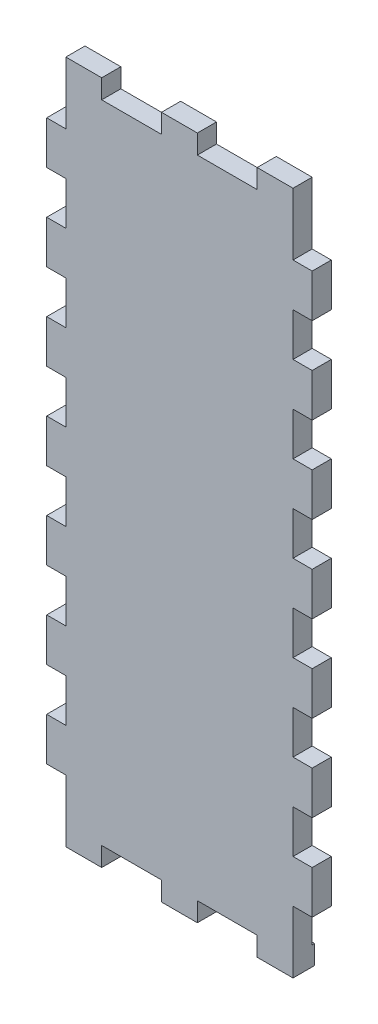
SolidWorks part; units mm, degrees
material "Beech"
ref_plane "Front" through (0, 0, 0) normal (0, 0, 1) x (1, 0, 0)
ref_plane "Top" through (0, 0, 0) normal (0, 1, 0) x (1, 0, 0)
ref_plane "Right" through (0, 0, 0) normal (1, 0, 0) x (0, 0, -1)
sketch "Sketch1" plane through (0, 0, 0) normal (0, 0, 1) x (1, 0, 0)
  line L1 (-47.5, -135) -> (47.5, -135)
  line L2 (-47.5, -135) -> (-47.5, 135)
  line L3 (-47.5, 135) -> (47.5, 135)
  line L4 (47.5, -135) -> (47.5, 135)
  line L5 (-47.5, -135) -> (47.5, 135) construction
  line L6 (-47.5, 135) -> (47.5, -135) construction
  point P0 (0, 0)
  dimension "D1" = 270
  dimension "D2" = 95
extrude "Boss-Extrude1" add sketch "Sketch1" along normal blind 8
sketch "Sketch2" plane through (0, -135, 0) normal (0, -1, 0) x (1, 0, 0)
  line L0 (0, 0) -> (0, 8) construction
  line L1 (-47.5, 8) -> (-32.5, 8)
  line L2 (-47.5, 8) -> (-47.5, -1)
  line L3 (-47.5, -1) -> (-32.5, -1)
  line L4 (-32.5, 8) -> (-32.5, -1)
  line L5 (-47.5, 8) -> (-32.5, -1) construction
  line L6 (-47.5, -1) -> (-32.5, 8) construction
  line L7 (-47.5, 8) -> (47.5, 8) construction
  line L8 (7.5, 0) -> (-7.5, 0)
  line L9 (-47.5, 0) -> (47.5, 0) construction
  line L10 (-7.5, 0) -> (-7.5, 8)
  line L11 (-7.5, 8) -> (7.5, 8)
  line L12 (47.5, -1) -> (32.5, -1)
  line L13 (47.5, 8) -> (47.5, -1)
  line L14 (47.5, 8) -> (32.5, 8)
  line L15 (32.5, 8) -> (32.5, -1)
  line L16 (7.5, 0) -> (7.5, 8)
  point P4 (-40, 3.5)
  dimension "D1" = 15
  dimension "D2" = 9
  dimension "D3" = 7.5
extrude "Boss-Extrude2" add sketch "Sketch2" along normal blind 8
sketch "Sketch4" plane through (47.5, 0, 0) normal (1, 0, 0) x (0, 0, -1)
  line L0 (-8, -143) -> (-8, 135) construction
  line L1 (-8, 117) -> (0, 117)
  line L2 (-8, 117) -> (-8, 99)
  line L3 (-8, 99) -> (0, 99)
  line L4 (0, 117) -> (0, 99)
  line L5 (-8, 117) -> (0, 99) construction
  line L6 (-8, 99) -> (0, 117) construction
  line L7 (0, -135) -> (0, 135) construction
  line L8 (-8, 135) -> (0, 135) construction
  line L9 (0, 81) -> (0, 63)
  line L10 (-8, 63) -> (0, 63)
  line L11 (-8, 81) -> (-8, 63)
  line L12 (-8, 81) -> (0, 81)
  line L13 (0, 45) -> (0, 27)
  line L14 (-8, 27) -> (0, 27)
  line L15 (-8, 45) -> (-8, 27)
  line L16 (-8, 45) -> (0, 45)
  line L17 (0, 9) -> (0, -9)
  line L18 (-8, -9) -> (0, -9)
  line L19 (-8, 9) -> (-8, -9)
  line L20 (-8, 9) -> (0, 9)
  line L21 (0, -27) -> (0, -45)
  line L22 (-8, -45) -> (0, -45)
  line L23 (-8, -27) -> (-8, -45)
  line L24 (-8, -27) -> (0, -27)
  line L25 (0, -63) -> (0, -81)
  line L26 (-8, -81) -> (0, -81)
  line L27 (-8, -63) -> (-8, -81)
  line L28 (-8, -63) -> (0, -63)
  line L29 (0, -99) -> (0, -117)
  line L30 (-8, -117) -> (0, -117)
  line L31 (-8, -99) -> (-8, -117)
  line L32 (-8, -99) -> (0, -99)
  point P4 (-4, 108)
  dimension "D1" = 18
  dimension "D2" = 18
  dimension "D3" = 7
  dimension "D4" = 18
extrude "Boss-Extrude3" add sketch "Sketch4" along normal blind 8
sketch "Sketch5" plane through (-47.5, 0, 0) normal (-1, 0, 0) x (0, 0, 1)
  line L0 (0, 135) -> (0, -135) construction
  line L1 (0, 117) -> (8, 117)
  line L2 (0, 117) -> (0, 99)
  line L3 (0, 99) -> (8, 99)
  line L4 (8, 117) -> (8, 99)
  line L5 (0, 117) -> (8, 99) construction
  line L6 (0, 99) -> (8, 117) construction
  line L7 (8, 135) -> (8, -143) construction
  line L8 (8, 135) -> (0, 135) construction
  line L9 (8, 81) -> (8, 63)
  line L10 (0, 63) -> (8, 63)
  line L11 (0, 81) -> (0, 63)
  line L12 (0, 81) -> (8, 81)
  line L13 (8, 45) -> (8, 27)
  line L14 (0, 27) -> (8, 27)
  line L15 (0, 45) -> (0, 27)
  line L16 (0, 45) -> (8, 45)
  line L17 (8, 9) -> (8, -9)
  line L18 (0, -9) -> (8, -9)
  line L19 (0, 9) -> (0, -9)
  line L20 (0, 9) -> (8, 9)
  line L21 (8, -27) -> (8, -45)
  line L22 (0, -45) -> (8, -45)
  line L23 (0, -27) -> (0, -45)
  line L24 (0, -27) -> (8, -27)
  line L25 (8, -63) -> (8, -81)
  line L26 (0, -81) -> (8, -81)
  line L27 (0, -63) -> (0, -81)
  line L28 (0, -63) -> (8, -63)
  line L29 (8, -99) -> (8, -117)
  line L30 (0, -117) -> (8, -117)
  line L31 (0, -99) -> (0, -117)
  line L32 (0, -99) -> (8, -99)
  point P4 (4, 108)
  dimension "D1" = 18
  dimension "D2" = 18
  dimension "D4" = 18
  dimension "D3" = 7
extrude "Boss-Extrude4" add sketch "Sketch5" along normal blind 8
sketch "Sketch6" plane through (0, 135, 0) normal (0, 1, 0) x (1, 0, 0)
  line L0 (47.5, 0) -> (-47.5, 0) construction
  line L1 (-47.5, -8) -> (-32.5, -8)
  line L2 (-47.5, -8) -> (-47.5, 0)
  line L3 (-47.5, 0) -> (-32.5, 0)
  line L4 (-32.5, -8) -> (-32.5, 0)
  line L5 (-47.5, -8) -> (-32.5, 0) construction
  line L6 (-47.5, 0) -> (-32.5, -8) construction
  line L7 (7.5, 0) -> (-7.5, 0)
  line L8 (-7.5, 0) -> (-7.5, -8)
  line L9 (47.5, -8) -> (-47.5, -8) construction
  line L10 (-7.5, -8) -> (7.5, -8)
  line L11 (0, -8) -> (0, 0) construction
  line L12 (47.5, -8) -> (32.5, -8)
  line L13 (47.5, -8) -> (47.5, 0)
  line L14 (47.5, 0) -> (32.5, 0)
  line L15 (32.5, -8) -> (32.5, 0)
  line L16 (7.5, 0) -> (7.5, -8)
  point P4 (-40, -4)
  dimension "D1" = 7.5
  dimension "D2" = 15
extrude "Boss-Extrude5" add sketch "Sketch6" along normal blind 8
